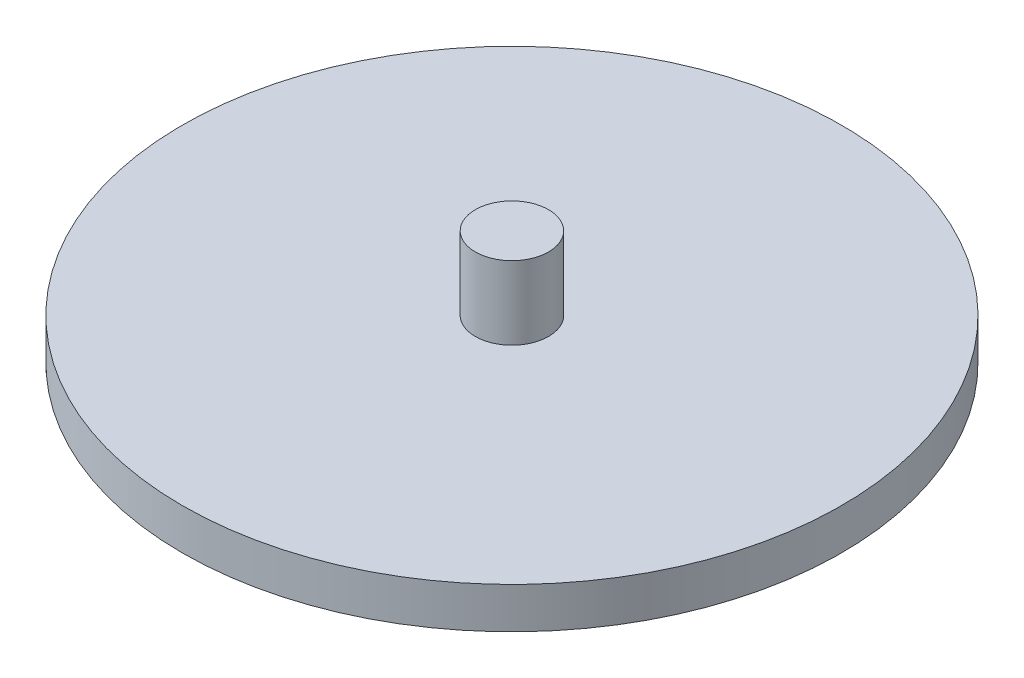
SolidWorks part; units mm, degrees
ref_plane "Front Plane" through (0, 0, 0) normal (0, 0, 1) x (1, 0, 0)
ref_plane "Top Plane" through (0, 0, 0) normal (0, 1, 0) x (1, 0, 0)
ref_plane "Right Plane" through (0, 0, 0) normal (1, 0, 0) x (0, 0, -1)
sketch "Sketch1" plane through (0, 0, 0) normal (0, 1, 0) x (1, 0, 0)
  circle A0 centre (0, 0) radius 45
  circle A1 centre (0, 0) radius 5
  dimension "D1" = 90
  dimension "D2" = 10
extrude "Boss-Extrude1" add sketch "Sketch1" along normal mid plane 5.6 contours A0
sketch "Sketch3" plane through (0, 2.8, 0) normal (0, 1, 0) x (1, 0, 0)
  circle A0 centre (0, 0) radius 5
  dimension "D1" = 10
extrude "Boss-Extrude2" add sketch "Sketch3" along normal blind 10
extrude "Boss-Extrude3" add sketch "Sketch3<2>" against normal blind 15
sketch "Sketch3<2>" plane through (0, 2.8, 0) normal (0, 1, 0) x (1, 0, 0) same geometry as "Sketch3"
